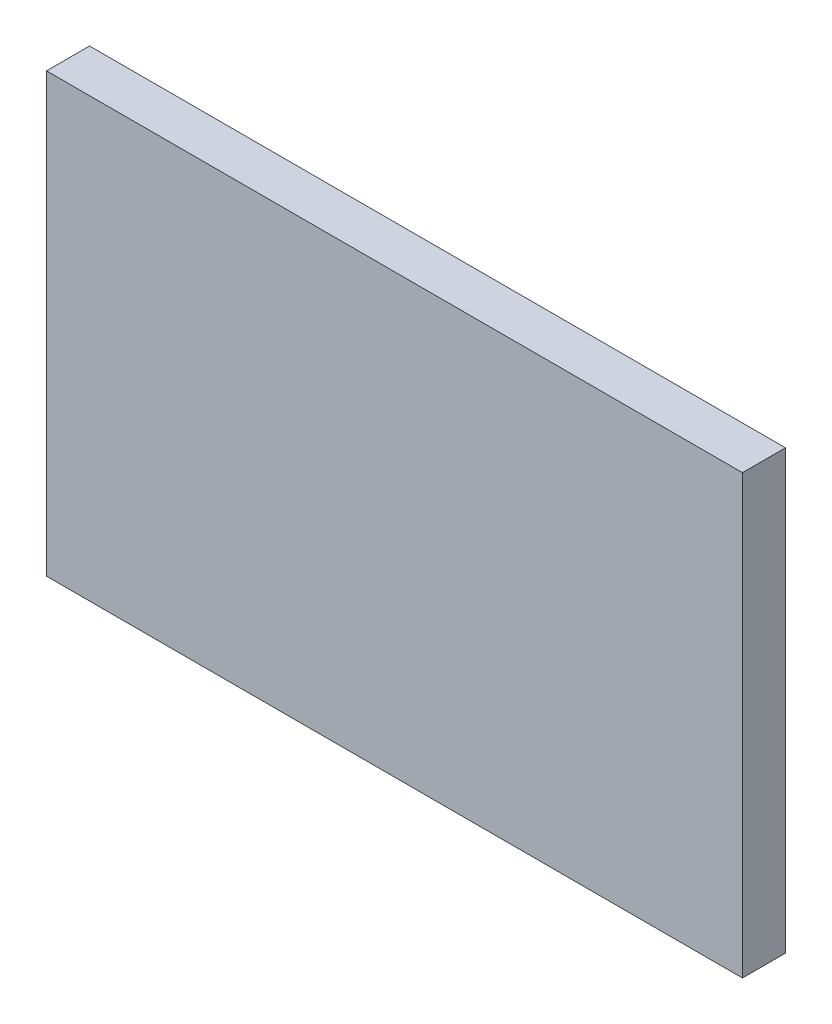
SolidWorks part; units mm, degrees
ref_plane "Front Plane" through (0, 0, 0) normal (0, 0, 1) x (1, 0, 0)
ref_plane "Top Plane" through (0, 0, 0) normal (0, 1, 0) x (1, 0, 0)
ref_plane "Right Plane" through (0, 0, 0) normal (1, 0, 0) x (0, 0, -1)
sketch "Sketch1" plane through (0, 0, 0) normal (0, 0, 1) x (1, 0, 0)
  line L0 (-152.4, 0) -> (155.575, 0) construction
  line L5 (155.575, -88.9) -> (-152.4, -88.9)
  line L7 (155.575, 104.775) -> (-152.4, 104.775)
  line L11 (-152.4, 104.775) -> (-152.4, 0)
  line L12 (-152.4, 0) -> (-152.4, -88.9)
  line L13 (155.575, 104.775) -> (155.575, 0)
  line L14 (155.575, 0) -> (155.575, -88.9)
  point P0 (0, 0)
  dimension "D1" = 307.975
  dimension "D2" = 104.775
  dimension "D3" = 88.9
extrude "Boss-Extrude1" add sketch "Sketch1" along normal blind 19.05
